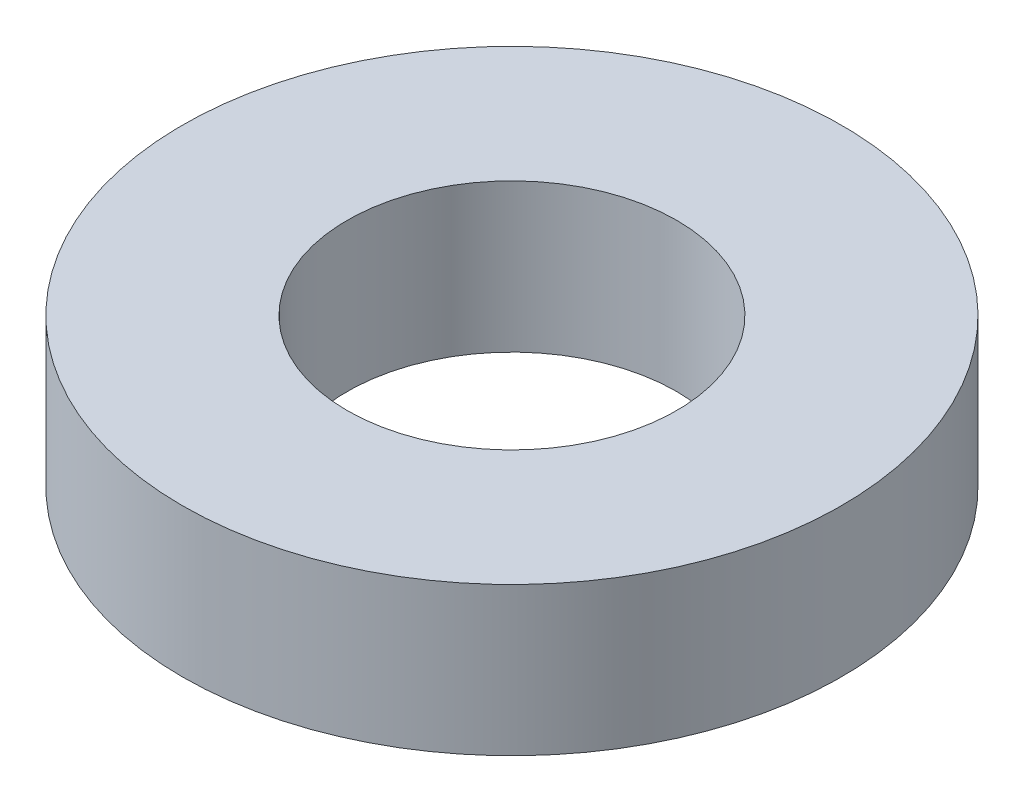
SolidWorks part; units mm, degrees
ref_plane "Front Plane" through (0, 0, 0) normal (0, 0, 1) x (1, 0, 0)
ref_plane "Top Plane" through (0, 0, 0) normal (0, 1, 0) x (1, 0, 0)
ref_plane "Right Plane" through (0, 0, 0) normal (1, 0, 0) x (0, 0, -1)
sketch "Sketch1" plane through (0, 0, 0) normal (0, 1, 0) x (1, 0, 0)
  circle A0 centre (0, 0) radius 60
  dimension "FLANGE_OD" = 120
extrude "Boss-Extrude1" add sketch "Sketch1" along normal blind 27
sketch "Sketch2" plane through (0, 0, 0) normal (0, 1, 0) x (1, 0, 0)
  circle A0 centre (0, 0) radius 30
  dimension "BORE_D" = 60
extrude "Cut-Extrude1" cut sketch "Sketch2" along normal through all
sketch "Sketch3" plane through (0, 27, 0) normal (0, 1, 0) x (1, 0, 0)
  circle A0 centre (0, 0) radius 25.6722 construction
  circle A1 centre (-25.6722, 0) radius 2.527
  dimension "BOLT_D" = 5.0539
  dimension "BOLT_PCD" = 51.3445
extrude "Cut-Extrude2" cut sketch "Sketch3" against normal blind 18.4707 rebuild error yes
pattern_circular "CirPattern1" count 8 over 360 rebuild error yes
